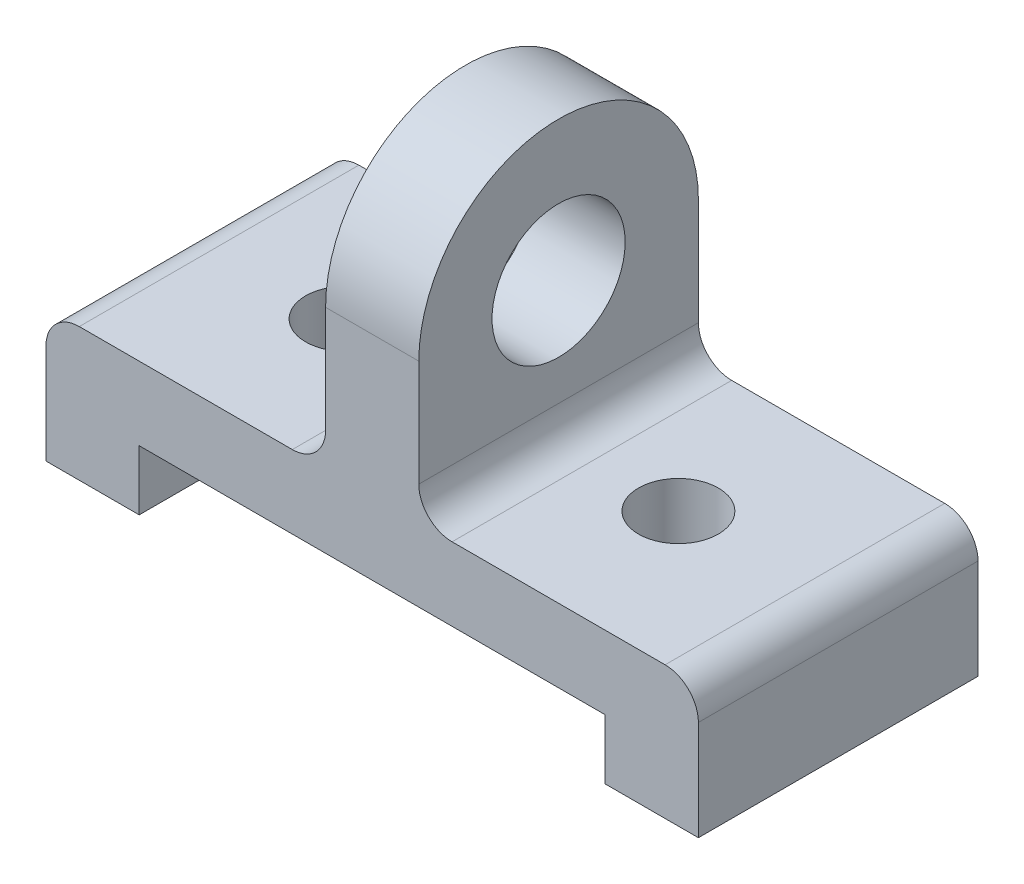
SolidWorks part; units mm, degrees
ref_plane "Front Plane" through (0, 0, 0) normal (0, 0, 1) x (1, 0, 0)
ref_plane "Top Plane" through (0, 0, 0) normal (0, 1, 0) x (1, 0, 0)
ref_plane "Right Plane" through (0, 0, 0) normal (1, 0, 0) x (0, 0, -1)
sketch "Sketch1" plane through (0, 0, 0) normal (0, 1, 0) x (1, 0, 0)
  line L1 (-49, 21) -> (49, 21)
  line L2 (-49, 21) -> (-49, -21)
  line L3 (-49, -21) -> (49, -21)
  line L4 (49, 21) -> (49, -21)
  line L5 (-49, 21) -> (49, -21) construction
  line L6 (-49, -21) -> (49, 21) construction
  point P0 (0, 0)
  dimension "D1" = 98
  dimension "D2" = 42
extrude "Boss-Extrude1" add sketch "Sketch1" along normal mid plane 20
sketch "Sketch2" plane through (0, 0, 21) normal (0, 0, 1) x (1, 0, 0)
  line L0 (-35, -1) -> (35, -1)
  line L1 (35, -1) -> (35, -10)
  line L2 (-49, -10) -> (49, -10) construction
  line L3 (35, -10) -> (-35, -10)
  line L4 (-35, -10) -> (-35, -1)
  line L5 (-49, 10) -> (-49, -10) construction
  line L6 (49, 10) -> (49, -10) construction
  dimension "D1" = 9
  dimension "D2" = 14
  dimension "D3" = 14
extrude "Cut-Extrude1" cut sketch "Sketch2" against normal blind 42
sketch "Sketch4" plane through (0, 0, 0) normal (1, 0, 0) x (0, 0, -1)
  line L0 (-21, 10) -> (-21, 52)
  line L1 (21, 10) -> (21, 52)
  line L2 (21, 52) -> (-21, 52)
  line L3 (-21, 10) -> (21, 10)
  dimension "D1" = 42
extrude "Boss-Extrude3" add sketch "Sketch4" along normal mid plane 14
fillet "Fillet1" 2 edges at (0, 52, 21) (0, 52, -21) type full round first side face at (0, 8.5, 21) second side face at (0, 8.5, -21) middle face at (0, 52, 0)
sketch "Sketch5" plane through (7, 0, 0) normal (1, 0, 0) x (0, 0, -1)
  circle A0 centre (0, 31) radius 10
  dimension "D2" = 20
extrude "Cut-Extrude2" cut sketch "Sketch5" against normal blind 14
sketch "Sketch6" plane through (0, 10, 0) normal (0, 1, 0) x (1, 0, 0)
  line L0 (0, 32.8246) -> (0, -42.6813) construction
  circle A0 centre (25, 0) radius 6
  circle A1 centre (-25, 0) radius 6
  dimension "D2" = 12
extrude "Cut-Extrude3" cut sketch "Sketch6" against normal blind 14
fillet "Fillet2" radius 5 2 edges at (-49, 10, 0) (49, 10, 0)
fillet "Fillet3" radius 5 2 edges at (-7, 10, 0) (7, 10, 0)
